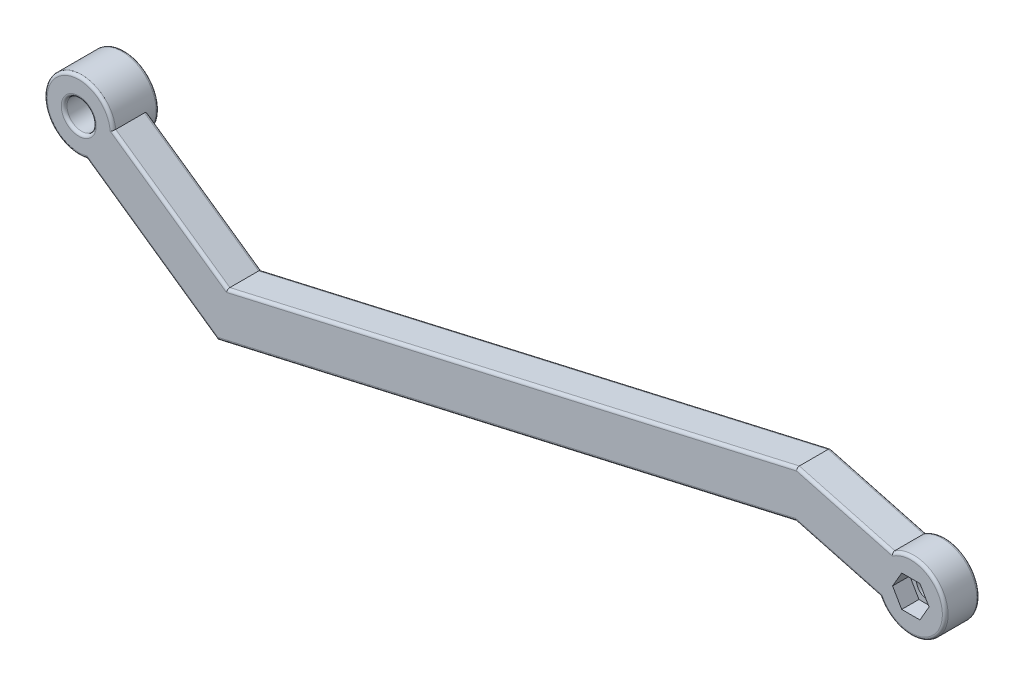
SolidWorks part; units mm, degrees
ref_plane "前视基准面" through (0, 0, 0) normal (0, 0, 1) x (1, 0, 0)
ref_plane "上视基准面" through (0, 0, 0) normal (0, 1, 0) x (1, 0, 0)
ref_plane "右视基准面" through (0, 0, 0) normal (1, 0, 0) x (0, 0, -1)
other "Configuration Table"
sketch "草图1" plane through (0, 0, 0) normal (0, 0, 1) x (1, 0, 0)
  line L0 (0, 0) -> (-145, 0) construction
  line L3 (-145, 0) -> (-120, -17.5052) construction
  line L4 (-120, -17.5052) -> (-20, 5.359) construction
  line L5 (-20, 5.359) -> (0, 0) construction
  line L7 (-142.7057, 3.2766) -> (-119.1604, -13.21)
  line L8 (-147.2943, -3.2766) -> (-120.8396, -21.8004)
  line L10 (-120.8396, -21.8004) -> (-20.0763, 1.2383)
  line L11 (-20.0763, 1.2383) -> (-1.0353, -3.8637)
  line L12 (1.0353, 3.8637) -> (-19.9237, 9.4796)
  line L13 (-19.9237, 9.4796) -> (-119.1604, -13.21)
  arc A0 (-3.2845, 5.0212) -> (-5.355, -2.7062) centre (0, 0) cw
  arc A1 (-139.0423, 0.7115) -> (-143.6309, -5.8417) centre (-145, 0) ccw
  circle A2 centre (-145, 0) radius 4
  circle A3 centre (0, 0) radius 4
  circle A4 centre (-145, 0) radius 2.55
  circle A5 centre (0, 0) radius 2.05
  dimension "D2" = 6
  dimension "D3" = 8
  dimension "D6" = 5.1
  dimension "D7" = 4.1
  dimension "D1" = 145
  dimension "D4" = 25
  dimension "D5" = 35
  dimension "D8" = 15
  dimension "D9" = 20
  dimension "D10" = 4
  dimension "D11" = 4
extrude "凸台-拉伸1" add sketch "草图1" along normal mid plane 6 contours A2 A4 | A2 L7 A1 L8 | A3 L12 L13 L7 A2 L8 L10 L11 | A3 L11 A0 L12 | A3 A5 region at (-148.4154, 2.3915, 0) region at (-74.4027, -5.6599, 0) region at (-141.5523, 1.7948, 0) region at (5.636, -1.5102, 0) region at (3.0837, 2.3662, 0)
ref_axis "后基准轴" through (0, 0, 0) along (0, 0, 1)
ref_axis "前基准轴" through (-145, 0, 0) along (0, 0, 1)
sketch "草图2" plane through (0, 0, -3) normal (0, 0, 1) x (1, 0, 0)
  circle A0 centre (-145, 0) radius 2.55
  circle A1 centre (-145, 0) radius 6
  circle A2 centre (-145, 0) radius 2.55 construction
  arc A3 (-139.0423, 0.7115) -> (-143.6309, -5.8417) centre (-145, 0) ccw construction
extrude "凸台-拉伸2" add sketch "草图2" against normal blind 2 contours A1 A0 region at (-150.8303, 0, -3)
sketch "草图3" plane through (0, 0, 3) normal (0, 0, 1) x (1, 0, 0)
  line L1 (1.5877, -2.75) -> (3.1754, 0)
  line L2 (3.1754, 0) -> (1.5877, 2.75)
  line L3 (1.5877, 2.75) -> (-1.5877, 2.75)
  line L4 (-1.5877, 2.75) -> (-3.1754, 0)
  line L5 (-3.1754, 0) -> (-1.5877, -2.75)
  line L6 (-1.5877, -2.75) -> (1.5877, -2.75)
  circle A0 centre (0, 0) radius 2.75 construction
  dimension "D1" = 5.5
extrude "切除-拉伸1" cut sketch "草图3" against normal blind 3
fillet "圆角1" radius 0.5 19 edges at (-12.7157, -0.734, -3) (-132.2353, -13.8211, -3) (-70.458, -10.281, -3) (-69.542, -1.8652, 3) (-129.1014, -6.2492, 3) (-132.2353, -13.8211, 3) (-151, 0, -5) (-129.1014, -6.2492, -3) (-69.542, -1.8652, -3) (5.7956, -1.5529, -3) (-11.6041, 7.2504, -3) (-11.6041, 7.2504, 3) (5.7956, -1.5529, 3) (-12.7157, -0.734, 3) (-70.458, -10.281, 3) (2.05, 0, -3) (-147.55, 0, -5) (-142.45, 0, 3) (-149.9149, 3.4415, 3)
